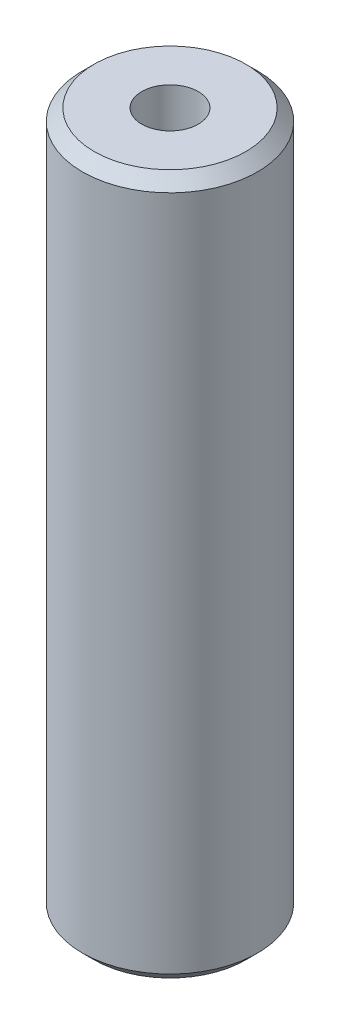
SolidWorks part; units mm, degrees
ref_plane "Front Plane" through (0, 0, 0) normal (0, 0, 1) x (1, 0, 0)
ref_plane "Top Plane" through (0, 0, 0) normal (0, 1, 0) x (1, 0, 0)
ref_plane "Right Plane" through (0, 0, 0) normal (1, 0, 0) x (0, 0, -1)
sketch "Sketch1" plane through (0, 0, 0) normal (0, 1, 0) x (1, 0, 0)
  circle A0 centre (0, 0) radius 25
  dimension "SHAFT_OD" = 50
extrude "Boss-Extrude1" add sketch "Sketch1" along normal blind 199.973
sketch "Sketch2" plane through (0, 0, 0) normal (0, 1, 0) x (1, 0, 0)
  circle A0 centre (0, 0) radius 8.0804
  dimension "BORE_D" = 16.1608
extrude "Cut-Extrude1" cut sketch "Sketch2" along normal through all
chamfer "Chamfer1" distance 3.3483 angle 45 2 edges at (0, 199.973, 25) (0, 0, 25)
